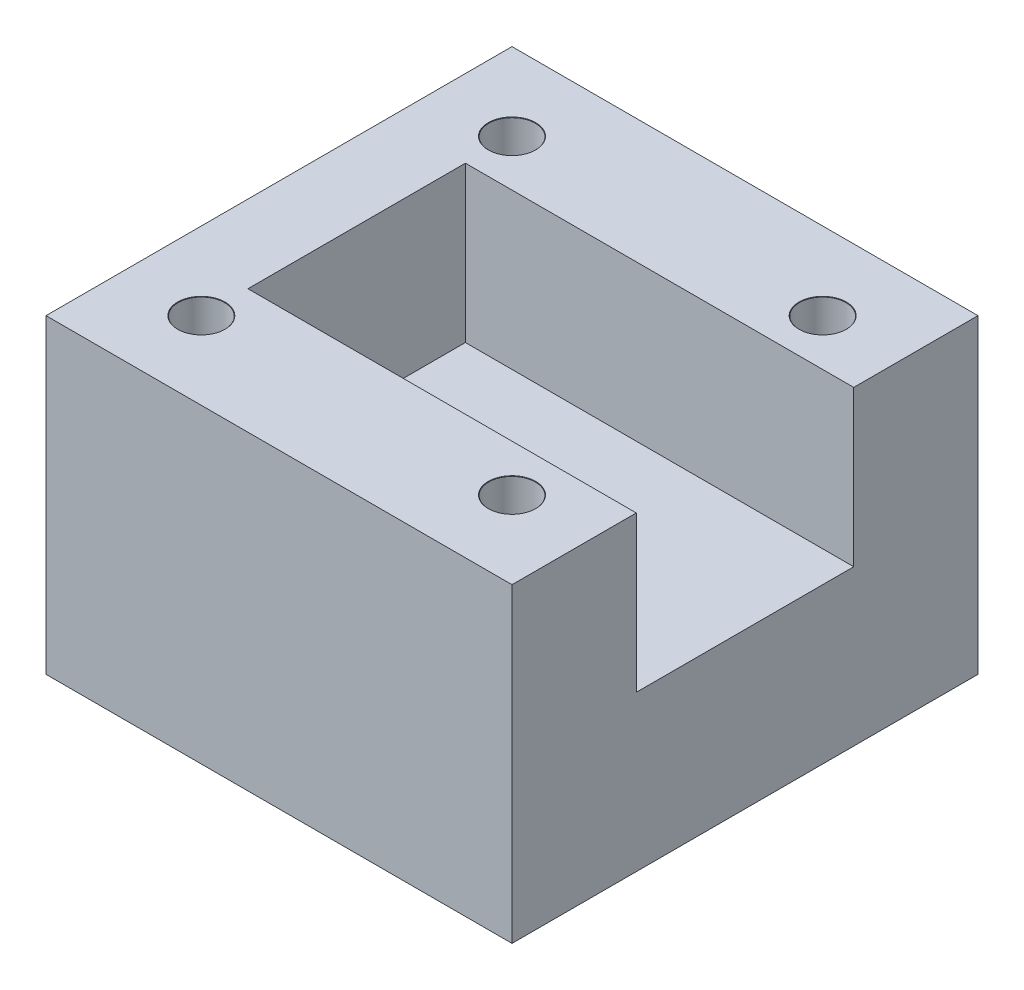
SolidWorks part; units mm, degrees
ref_plane "Front Plane" through (0, 0, 0) normal (0, 0, 1) x (1, 0, 0)
ref_plane "Top Plane" through (0, 0, 0) normal (0, 1, 0) x (1, 0, 0)
ref_plane "Right Plane" through (0, 0, 0) normal (1, 0, 0) x (0, 0, -1)
sketch "Sketch1" plane through (0, 23, 0) normal (0, 1, 0) x (1, 0, 0)
  line L0 (-288.3664, -197.9247) -> (-288.3664, -251.1066) construction
  line L5 (-273.3664, -205.9841) -> (-303.3664, -205.9841)
  line L6 (-273.3664, -205.9841) -> (-273.3664, -235.9841)
  line L7 (-273.3664, -235.9841) -> (-303.3664, -235.9841)
  line L8 (-303.3664, -205.9841) -> (-303.3664, -235.9841)
  line L9 (-273.3664, -220.9841) -> (-329.346, -220.9841) construction
  line L11 (-298.3664, -210.9841) -> (-278.3664, -210.9841) construction
  line L12 (-298.3664, -210.9841) -> (-298.3664, -230.9841) construction
  line L13 (-298.3664, -230.9841) -> (-278.3664, -230.9841) construction
  line L14 (-278.3664, -210.9841) -> (-278.3664, -230.9841) construction
  line L15 (-298.3664, -210.9841) -> (-278.3664, -230.9841) construction
  line L16 (-298.3664, -230.9841) -> (-278.3664, -210.9841) construction
  point P6 (-288.3664, -220.9841)
  point P14 (-288.3664, -235.9841)
  point P15 (-303.3664, -220.9841)
  point P17 (-302.3592, -214.2243)
  point P18 (-322.3592, -214.2243)
  point P19 (-322.3592, -234.2243)
  point P20 (-302.3592, -234.2243)
  dimension "D1" = 30
  dimension "D2" = 30
  dimension "D3" = 20
  dimension "D4" = 20
extrude "Boss-Extrude1" add sketch "Sketch1" along normal blind 20
sketch "Sketch2" plane through (0, 43, 0) normal (0, 1, 0) x (1, 0, 0)
  line L0 (-288.3664, -235.9841) -> (-288.3664, -181.7703) construction
  line L1 (-303.3664, -235.9841) -> (-273.3664, -235.9841) construction
  line L2 (-303.3664, -220.9841) -> (-253.0225, -220.9841) construction
  line L3 (-303.3664, -205.9841) -> (-303.3664, -235.9841) construction
  line L4 (-273.3664, -235.9841) -> (-273.3664, -205.9841) construction
  line L5 (-298.3664, -213.9841) -> (-273.3664, -213.9841)
  line L6 (-298.3664, -213.9841) -> (-298.3664, -227.9841)
  line L7 (-298.3664, -227.9841) -> (-273.3664, -227.9841)
  line L8 (-273.3664, -213.9841) -> (-273.3664, -227.9841)
  point P14 (-298.3664, -220.9841)
  dimension "D1" = 14
  dimension "D2" = 25
extrude "Cut-Extrude1" cut sketch "Sketch2" against normal blind 10
hole_wizard "Ø3.0mm Dowel Hole2" positions "Sketch8" profile "Sketch9" hole size "Ø3.0" standard "ANSI Metric" end condition through all
sketch "Sketch8" plane through (0, 43, 0) normal (0, 1, 0) x (1, 0, 0)
  point P0 (-298.3664, -210.9841)
  point P3 (-278.3664, -210.9841)
  point P6 (-278.3664, -230.9841)
  point P9 (-298.3664, -230.9841)
sketch "Sketch9" plane through (-298.3664, 43, 210.9841) normal (1, 0, 0) x (0, 0, 1)
  line L0 (0, 0) -> (0, 20)
  line L1 (0, 20) -> (1.5, 20)
  line L2 (1.5, 20) -> (1.5, 0.025)
  line L3 (1.5, 0.025) -> (1.525, 0)
  line L5 (1.525, 0) -> (0, 0)
  line L6 (-1.5, 0.025) -> (-1.525, 0) construction
  line L11 (0, -6.35) -> (0, 107.95) construction
  dimension "Thru Hole Dia." = 3
  dimension "Thru Hole Depth" = 20
  dimension "Near C'Sink Dia." = 3.05
  dimension "Near C'Sink Angle" = 90
